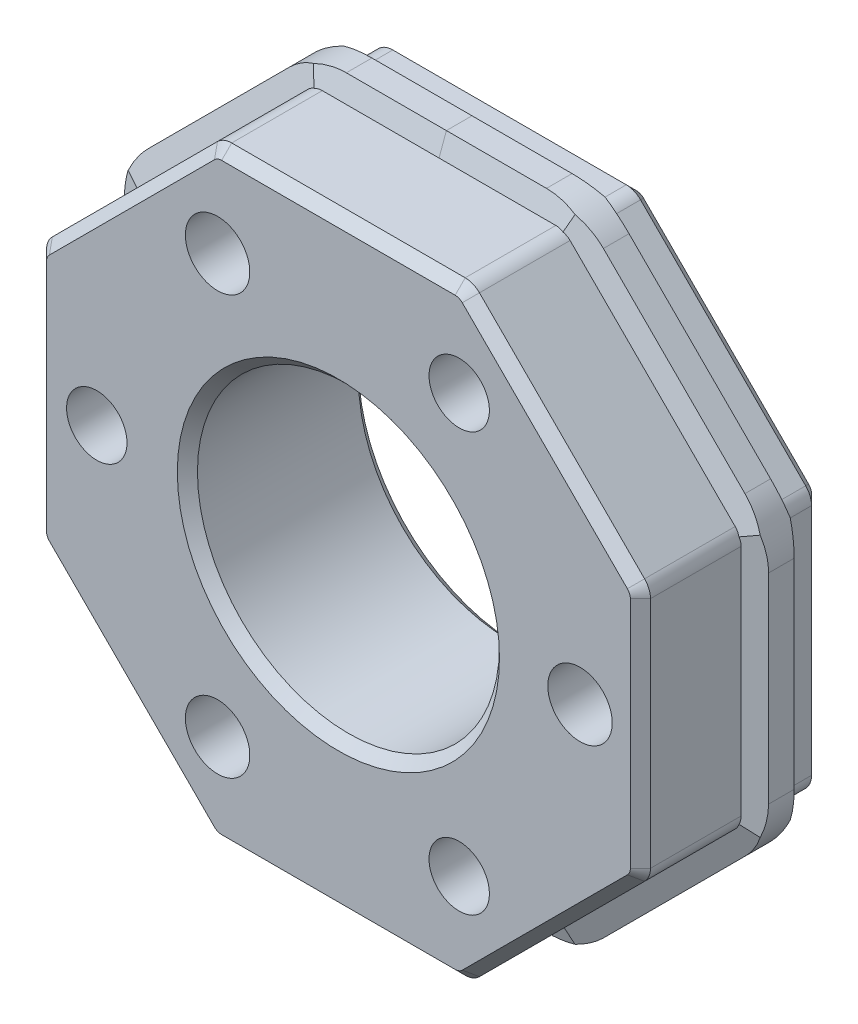
SolidWorks part; units mm, degrees
material "6061 合金"
ref_plane "前视基准面" through (0, 0, 0) normal (0, 0, 1) x (1, 0, 0)
ref_plane "上视基准面" through (0, 0, 0) normal (0, 1, 0) x (1, 0, 0)
ref_plane "右视基准面" through (0, 0, 0) normal (1, 0, 0) x (0, 0, -1)
other "Configuration Table"
sketch "草图1" plane through (0, 0, 0) normal (0, 0, 1) x (1, 0, 0)
  line L1 (-16, 16) -> (16, 16)
  line L2 (-16, 16) -> (-16, -16)
  line L3 (-16, -16) -> (16, -16)
  line L4 (16, 16) -> (16, -16)
  line L5 (0, -16) -> (0, 16) construction
  line L6 (-16, 0) -> (16, 0) construction
  circle A0 centre (0, 0) radius 7.5
  circle A1 centre (0, 0) radius 18 construction
  circle A2 centre (0, 0) radius 12 construction
  dimension "D1" = 36
  dimension "D2" = 15
  dimension "D3" = 24
  dimension "D6" = 32
  dimension "D7" = 32
extrude "凸台-拉伸1" add sketch "草图1" along normal mid plane 6
sketch "草图23" plane through (0, 0, 3) normal (0, 0, 1) x (1, 0, 0)
  line L0 (16, 16) -> (16, -16)
  line L8 (-16, -16) -> (16, -16)
  line L11 (16, -16) -> (16, 16)
  line L12 (16, -16) -> (16, 16)
  line L14 (16, 16) -> (-16, 16)
  line L15 (-16, 16) -> (-16, -16)
  line L16 (-16, -16) -> (16, -16)
  line L22 (16, 16) -> (-16, 16)
  line L23 (-16, 16) -> (-16, -16)
  line M23 (-16, -16) -> (16, -16)
  line M25 (16, -16) -> (16, 16)
  line M35 (16, 16) -> (-16, 16)
  line M37 (-16, 16) -> (-16, -16)
  circle M39 centre (0, 0) radius 7.5
  dimension "D1" = 0
extrude "凸台-拉伸4" add sketch "草图23" along normal blind 3 contours M23 M25 M35 M37 M39 region at (15.5475, 0, 3)
sketch "草图8" plane through (0, 0, -3) normal (0, 0, -1) x (-1, 0, 0)
  circle A0 centre (0, 0) radius 12 construction
  point P0 (-12, 0)
  point P1 (6, 10.3923)
  point P9 (6, -10.3923)
  dimension "D1" = 24
  dimension "D2" = 3
hole_wizard "M3 六角圆柱头螺钉的柱形沉头孔1" positions "草图8" profile "草图9" counterbore size "M3" standard "GB" end condition through all
sketch "草图9" plane through (12, 0, -3) normal (1, 0, 0) x (0, 1, 0)
  line L0 (0, 0) -> (0, 9)
  line L1 (0, 9) -> (1.6, 9)
  line L3 (1.6, 9) -> (1.6, 5)
  line L4 (1.6, 5) -> (2.85, 5)
  line L5 (2.85, 5) -> (2.85, 0)
  line L7 (2.85, 0) -> (0, 0)
  line L11 (0, -6.35) -> (0, 107.95) construction
  dimension "通孔孔直径" = 3.2
  dimension "通孔孔深度" = 9
  dimension "柱形沉头孔直径" = 5.7
  dimension "柱形沉头孔深度" = 5
sketch "草图24" plane through (0, 0, 6) normal (0, 0, 1) x (1, 0, 0)
  circle A0 centre (0, 0) radius 12 construction
  point P0 (-12, 0)
  point P13 (6, 10.3923)
  point P14 (6, -10.3923)
  dimension "D1" = 24
  dimension "D2" = 3
hole_wizard "Ø3.0mm 暗销孔1" positions "草图24" profile "草图25" hole size "Ø3.0" standard "BSI"
sketch "草图25" plane through (-12, 0, 6) normal (1, 0, 0) x (0, -1, 0)
  line L0 (0, 0) -> (0, 4.9013)
  line L1 (0, 4.9013) -> (1.5, 4)
  line L2 (1.5, 4) -> (1.5, 0)
  line L5 (1.5, 0) -> (0, 0)
  line L10 (0, 4.9013) -> (-1.5, 4) construction
  line L11 (0, -6.35) -> (0, 107.95) construction
  dimension "孔直径" = 3
  dimension "孔深度" = 4
  dimension "导头角度" = 118
ref_plane "基准面1" through (0, 0, 0) normal (0, 0, -1) x (-1, 0, 0)
sketch "草图26" plane through (0, 0, -3) normal (0, 0, -1) x (-1, 0, 0)
  circle A0 centre (0, 0) radius 15
  dimension "D1" = 30
extrude "切除-拉伸1" cut sketch "草图26" against normal through all flip side to cut
sketch "草图35" plane through (0, 0, 6) normal (0, 0, 1) x (1, 0, 0)
  line L0 (-18.5745, 0) -> (16.9837, 0) construction
ref_plane "基准面2" through (0, 0, 0) normal (0, -1, 0) x (1, 0, 0)
sketch "草图42" plane through (0, 0, -3) normal (0, 0, -1) x (-1, 0, 0)
  line L1 (-6.2132, 15) -> (-15, 6.2132)
  line L2 (-15, 6.2132) -> (-15, -6.2132)
  line L3 (-15, -6.2132) -> (-6.2132, -15)
  line L4 (-6.2132, -15) -> (6.2132, -15)
  line L5 (6.2132, -15) -> (15, -6.2132)
  line L6 (15, -6.2132) -> (15, 6.2132)
  line L7 (15, 6.2132) -> (6.2132, 15)
  line L8 (6.2132, 15) -> (-6.2132, 15)
  circle A0 centre (0, 0) radius 15 construction
  circle A1 centre (0, 0) radius 15 construction
  circle A2 centre (0, 0) radius 15
extrude "凸台-拉伸5" add sketch "草图42" against normal up to surface (9 mm away) contours A2 L8 L1 | A2 L7 L8 | A2 L6 L7 | A2 L5 L6 | A2 L4 L5 | A2 L3 L4 | A2 L2 L3 | A2 L1 L2 region at (5.8394, 14.0975, -3) region at (14.0975, 5.8394, -3) region at (-5.8394, 14.0975, -3) region at (14.0975, -5.8394, -3) region at (-14.0975, 5.8394, -3) region at (5.8394, -14.0975, -3) region at (-14.0975, -5.8394, -3) region at (-5.8394, -14.0975, -3) up to face at (7.5, 0, 6)
sketch "草图43" plane through (0, 0, 0) normal (1, 0, 0) x (0, 0, -1)
  line L1 (-1, 15) -> (1, 15)
  line L2 (-6, 15) -> (3, 15) construction
  line L3 (1, 15) -> (0.636, 16)
  line L4 (0.636, 16) -> (-0.636, 16)
  line L5 (-0.636, 16) -> (-1, 15)
  line L8 (3, 6.2132) -> (3, 15) construction
  line L9 (0, 22.7244) -> (0, -9.6288) construction
  dimension "D2" = 40
  dimension "D3" = 1
  dimension "D4" = 2
ref_plane "基准面3" through (0, 0, -1) normal (0, 0, -1) x (-1, 0, 0)
sketch "草图44" plane through (0, 0, -1) normal (0, 0, -1) x (-1, 0, 0)
  line L8 (-6.2132, 15) -> (-15, 6.2132)
  line L9 (-15, 6.2132) -> (-15, -6.2132)
  line L10 (-15, -6.2132) -> (-6.2132, -15)
  line L11 (-6.2132, -15) -> (6.2132, -15)
  line L12 (6.2132, -15) -> (15, -6.2132)
  line L13 (15, -6.2132) -> (15, 6.2132)
  line L14 (15, 6.2132) -> (6.2132, 15)
  line L15 (6.2132, 15) -> (-6.2132, 15)
  line L16 (-6.2132, 15) -> (-15, 6.2132)
  line L17 (-15, 6.2132) -> (-15, -6.2132)
  line L18 (-15, -6.2132) -> (-6.2132, -15)
  line L19 (-6.2132, -15) -> (6.2132, -15)
  line L20 (6.2132, -15) -> (15, -6.2132)
  line L21 (15, -6.2132) -> (15, 6.2132)
  line L22 (15, 6.2132) -> (6.2132, 15)
  line L23 (6.2132, 15) -> (-6.2132, 15)
  dimension "D1" = 0
sweep "扫描1" add profiles "草图43" path "草图44"
fillet "圆角1" radius 1 16 edges at (15, 6.2132, 3.5) (15, -6.2132, 3.5) (6.2132, -15, 3.5) (-6.2132, -15, 3.5) (-15, -6.2132, 3.5) (-15, 6.2132, 3.5) (6.2132, 15, 3.5) (-6.2132, 15, 3.5) (6.2132, 15, -2) (15, 6.2132, -2) (15, -6.2132, -2) (6.2132, -15, -2) (-6.2132, -15, -2) (-15, -6.2132, -2) (-15, 6.2132, -2) (-6.2132, 15, -2)
chamfer "倒角1" distance 0.5 angle 45 34 edges at (0, -15, -3) (-6.1817, -14.9239, -3) (6.1817, -14.9239, -3) (-10.6066, -10.6066, -3) (10.6066, -10.6066, -3) (-14.9239, -6.1817, -3) (14.9239, -6.1817, -3) (-15, 0, -3) (15, 0, -3) (-14.9239, 6.1817, -3) (14.9239, 6.1817, -3) (-10.6066, 10.6066, -3) (10.6066, 10.6066, -3) (-6.1817, 14.9239, -3) (6.1817, 14.9239, -3) (0, 15, -3) (0, -15, 6) (-6.1817, -14.9239, 6) (6.1817, -14.9239, 6) (-10.6066, -10.6066, 6) (10.6066, -10.6066, 6) (-14.9239, -6.1817, 6) (14.9239, -6.1817, 6) (-15, 0, 6) (15, 0, 6) (-14.9239, 6.1817, 6) (14.9239, 6.1817, 6) (-10.6066, 10.6066, 6) (10.6066, 10.6066, 6) (-6.1817, 14.9239, 6) (6.1817, 14.9239, 6) (0, 15, 6) (7.5, 0, 6) (7.5, 0, -3)
fillet "圆角2" radius 4 8 edges at (6.6274, 16, 0) (-6.6274, 16, 0) (-16, 6.6274, 0) (-16, -6.6274, 0) (-6.6274, -16, 0) (6.6274, -16, 0) (16, -6.6274, 0) (16, 6.6274, 0)
